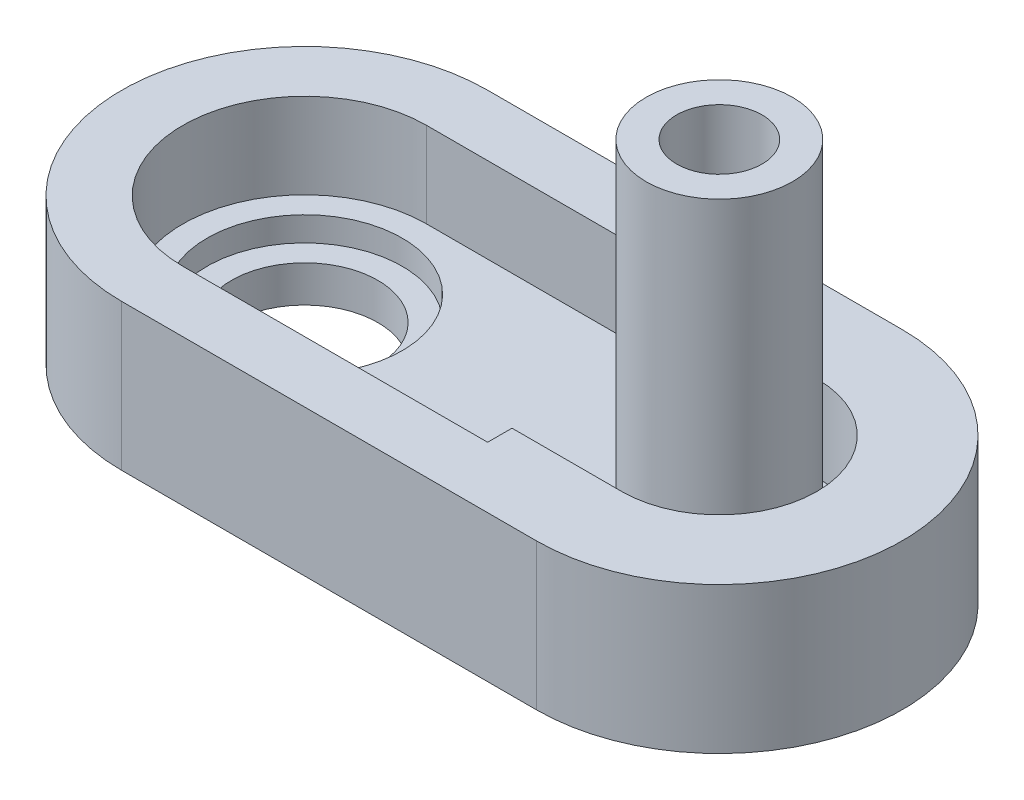
SolidWorks part; units mm, degrees
ref_plane "Front Plane" through (0, 0, 0) normal (0, 0, 1) x (1, 0, 0)
ref_plane "Top Plane" through (0, 0, 0) normal (0, 1, 0) x (1, 0, 0)
ref_plane "Right Plane" through (0, 0, 0) normal (1, 0, 0) x (0, 0, -1)
sketch "Sketch1" plane through (0, 0, 0) normal (0, 1, 0) x (1, 0, 0)
  line L0 (-33.6269, 0) -> (37.4767, 0) construction
  line L1 (0, 18.2669) -> (0, -20.8597) construction
  line L4 (-17, 0) -> (17, 0) construction
  line L5 (-17, 15) -> (17, 15)
  line L6 (-17, -15) -> (17, -15)
  arc A2 (-17, 15) -> (-17, -15) centre (-17, 0) ccw
  arc A3 (17, -15) -> (17, 15) centre (17, 0) ccw
  point P7 (0, 0)
  point P12 (0, 0)
  dimension "D1" = 15
  dimension "D2" = 34
extrude "Boss-Extrude1" add sketch "Sketch1" along normal blind 12
sketch "Sketch2" plane through (0, 12, 0) normal (0, 1, 0) x (1, 0, 0)
  line L0 (-39.3804, 0) -> (40.5611, 0) construction
  line L1 (8, 10) -> (-17, 10)
  line L2 (8, 8) -> (17, 8)
  line L3 (8, -8) -> (17, -8)
  line L4 (8, 8) -> (8, 10)
  line L6 (8, -8) -> (8, -10)
  line L8 (-27, 13.802) -> (-27, -19.8396) construction
  line L9 (8, -10) -> (-17, -10)
  line L10 (0, 20.7593) -> (0, -24.0778) construction
  arc A0 (17, 8) -> (17, -8) centre (17, 0) cw
  arc A3 (-17, -10) -> (-17, 10) centre (-17, 0) cw
  arc A4 (-17, 15) -> (-17, -15) centre (-17, 0) ccw construction
  arc A5 (17, -15) -> (17, 15) centre (17, 0) ccw construction
  point P12 (0, 0)
  point P18 (0, 0)
  point P25 (0, 0)
  point P26 (0, 0)
  dimension "D1" = 8
  dimension "D2" = 10
  dimension "D3" = 35
extrude "Cut-Extrude1" cut sketch "Sketch2" against normal blind 7 contours A3 L1 L4 L2 A0 L3 L6 L9
sketch "Sketch3" plane through (0, 5, 0) normal (0, 1, 0) x (1, 0, 0)
  line L0 (-39.2415, 0) -> (43.6866, 0) construction
  line L1 (0, 21.3571) -> (0, -22.7462) construction
  circle A0 centre (17, 0) radius 6
  circle A1 centre (17, 0) radius 3.5
  arc A2 (17, -8) -> (17, 8) centre (17, 0) ccw construction
  dimension "D1" = 12
  dimension "D2" = 7
extrude "Boss-Extrude2" add sketch "Sketch3" along normal blind 28
sketch "Sketch4" plane through (0, 5, 0) normal (0, 1, 0) x (1, 0, 0)
  circle A1 centre (17, 0) radius 3.5
  circle A2 centre (17, 0) radius 3.5
  dimension "D1" = 0
extrude "Cut-Extrude2" cut sketch "Sketch4" against normal blind 28
sketch "Sketch5" plane through (0, 5, 0) normal (0, 1, 0) x (1, 0, 0)
  line L0 (-40.0562, 0) -> (38.8047, 0) construction
  circle A0 centre (-17, 0) radius 6
  circle A1 centre (-17, 0) radius 8
  arc A2 (-17, 10) -> (-17, -10) centre (-17, 0) ccw construction
  dimension "D1" = 16
  dimension "D2" = 12
extrude "Cut-Extrude3" cut sketch "Sketch5" against normal blind 2 contours A1 L0 A0 | L0 A1 A0 region at (-17, 5, -6.1789) region at (-10, 5, 0.1789)
extrude "Cut-Extrude4" cut sketch "Sketch5<3>" against normal through all contours A0 L0 | L0 A0 region at (-17, 5, 2.5465) region at (-17, 5, -2.5465)
sketch "Sketch5<3>" plane through (0, 5, 0) normal (0, 1, 0) x (1, 0, 0) same geometry as "Sketch5"
